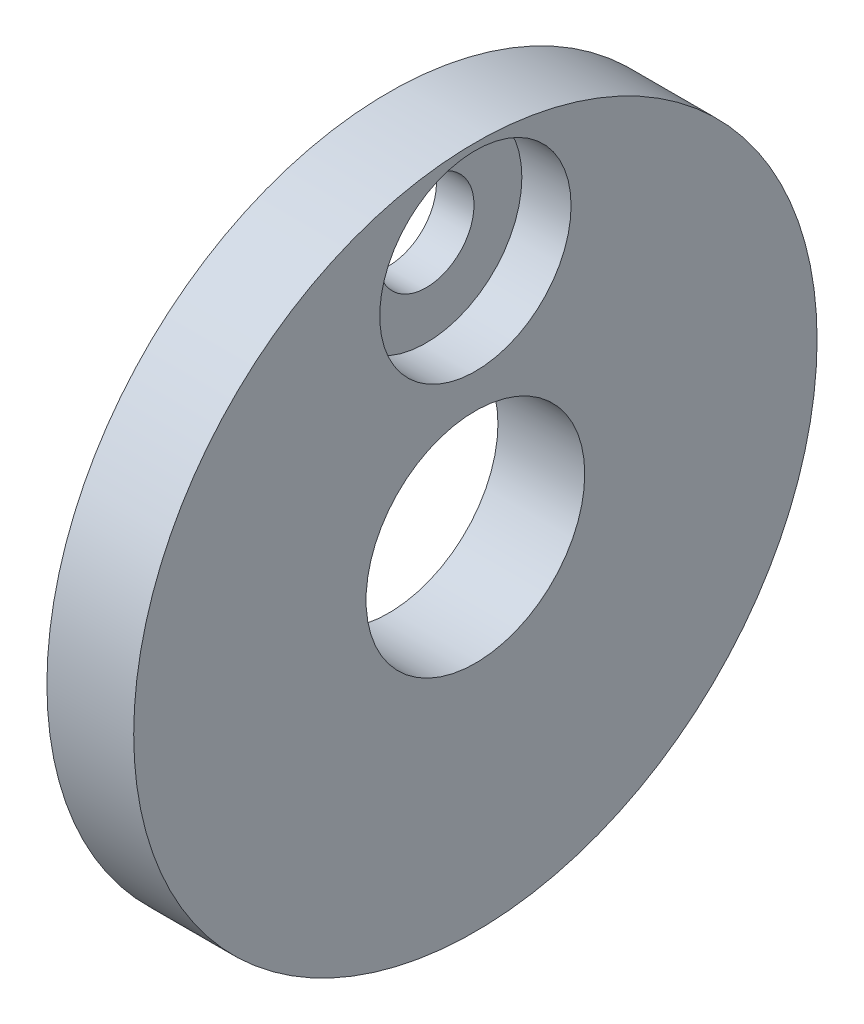
SolidWorks part; units mm, degrees
material "1023 Carbon Steel Sheet (SS)"
ref_plane "Front Plane" through (0, 0, 0) normal (0, 0, 1) x (1, 0, 0)
ref_plane "Top Plane" through (0, 0, 0) normal (0, 1, 0) x (1, 0, 0)
ref_plane "Right Plane" through (0, 0, 0) normal (1, 0, 0) x (0, 0, -1)
sketch "Sketch1" plane through (0, 0, 0) normal (1, 0, 0) x (0, 0, -1)
  circle A0 centre (0, 0) radius 12.5
  dimension "D1" = 25
extrude "Boss-Extrude1" add sketch "Sketch1" along normal blind 3.175
sketch "Sketch2" plane through (3.175, 0, 0) normal (1, 0, 0) x (0, 0, -1)
  circle A0 centre (0, 8.75) radius 1.75
  dimension "D1" = 3.5
  dimension "D2" = 8.75
sketch "Sketch3" plane through (3.175, 0, 0) normal (1, 0, 0) x (0, 0, -1)
  circle A0 centre (0, 0) radius 4
  dimension "D1" = 8
extrude "Cut-Extrude1" cut sketch "Sketch3" against normal through all
extrude "Cut-Extrude2" cut sketch "Sketch2" against normal through all
sketch "Sketch4" plane through (3.175, 0, 0) normal (1, 0, 0) x (0, 0, -1)
  line L1 (1.5877, 11.5) -> (-1.5877, 11.5)
  line L2 (-1.5877, 11.5) -> (-3.1754, 8.75)
  line L3 (-3.1754, 8.75) -> (-1.5877, 6)
  line L4 (-1.5877, 6) -> (1.5877, 6)
  line L5 (1.5877, 6) -> (3.1754, 8.75)
  line L6 (3.1754, 8.75) -> (1.5877, 11.5)
  circle A0 centre (0, 8.75) radius 2.75 construction
  circle A1 centre (0, 8.75) radius 3.5
  circle M13 centre (0, 8.75) radius 1.75
  dimension "D2" = 7
  dimension "D1" = 5.5
extrude "Cut-Extrude3" cut sketch "Sketch4" against normal blind 1.8 contours L5 L6 L1 L2 L3 L4 M13 | A1 L6 L5 L4 L3 L2 L1 | M13 | L1 L2 L3 L4 L5 L6 | A1 region at (3.175, 10.083, -2.3088) region at (3.175, 8.75, 3.401) region at (3.175, 8.75, 0)
